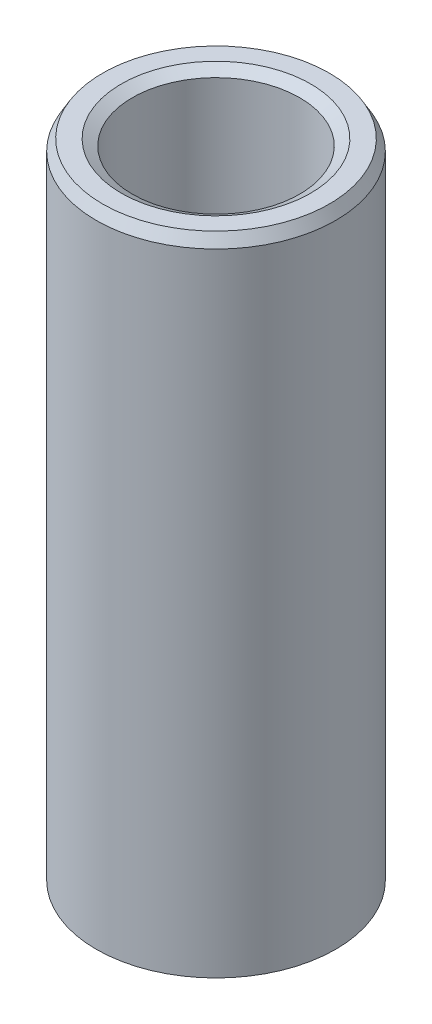
SolidWorks part; units mm, degrees
ref_plane "Front Plane" through (0, 0, 0) normal (0, 0, 1) x (1, 0, 0)
ref_plane "Top Plane" through (0, 0, 0) normal (0, 1, 0) x (1, 0, 0)
ref_plane "Right Plane" through (0, 0, 0) normal (1, 0, 0) x (0, 0, -1)
sketch "Sketch1" plane through (0, 0, 0) normal (0, 1, 0) x (1, 0, 0)
  circle A0 centre (0, 0) radius 40
  dimension "SLEEVE_OD" = 80
extrude "Boss-Extrude1" add sketch "Sketch1" along normal blind 216.6472
sketch "Sketch2" plane through (0, 0, 0) normal (0, 1, 0) x (1, 0, 0)
  circle A0 centre (0, 0) radius 27.9408
  dimension "BORE_D" = 55.8816
extrude "Cut-Extrude1" cut sketch "Sketch2" along normal through all
chamfer "Chamfer1" distance 3.687 angle 30 4 edges at (0, 216.6472, 27.9408) (0, 0, 27.9408) (0, 0, 40) (0, 216.6472, 40) first distance on face at (0, 216.6472, 27.9408) first distance on face at (0, 0, 27.9408) first distance on face at (0, 216.6472, 40)
